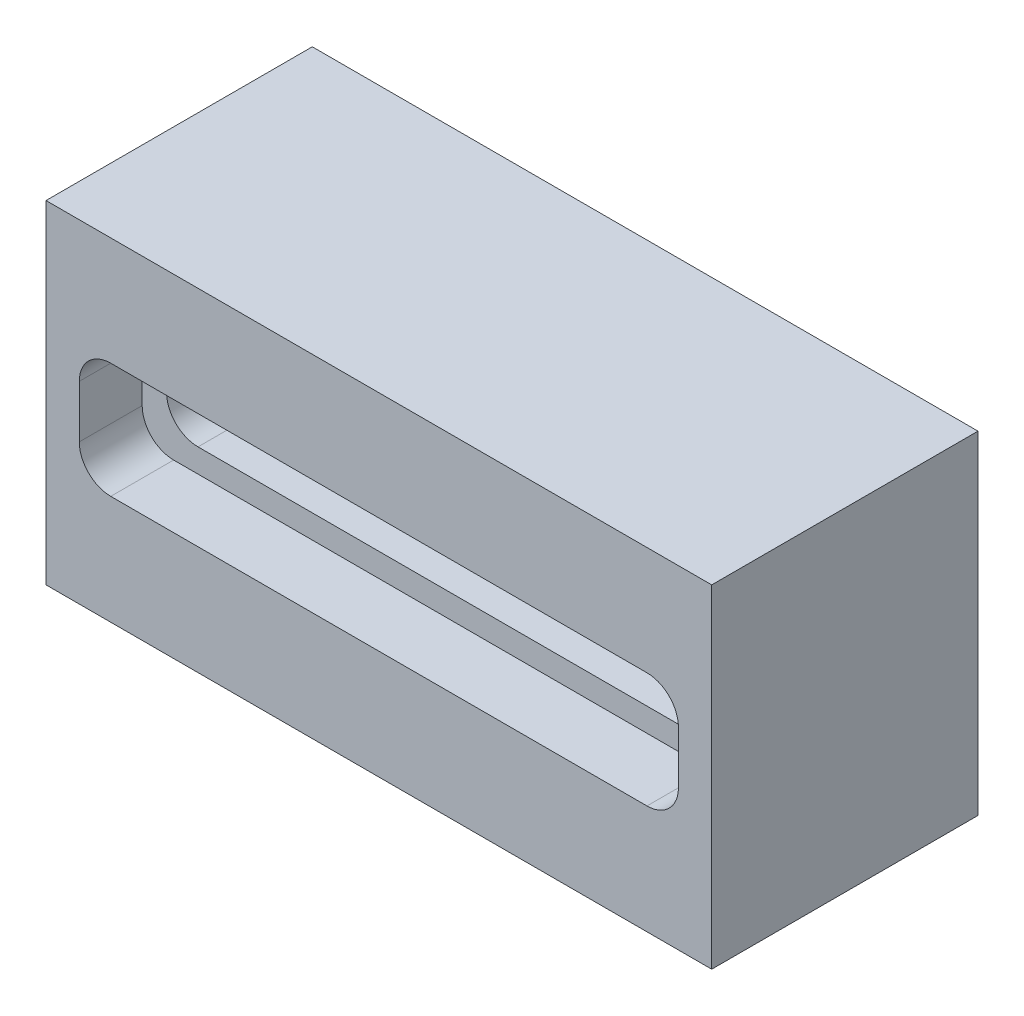
SolidWorks part; units mm, degrees
ref_plane "Front Plane" through (0, 0, 0) normal (0, 0, 1) x (1, 0, 0)
ref_plane "Top Plane" through (0, 0, 0) normal (0, 1, 0) x (1, 0, 0)
ref_plane "Right Plane" through (0, 0, 0) normal (1, 0, 0) x (0, 0, -1)
sketch "Sketch1" plane through (0, 0, 0) normal (0, 1, 0) x (1, 0, 0)
  line L1 (0, 0) -> (127, 0)
  line L2 (0, 0) -> (0, 50.8)
  line L3 (0, 50.8) -> (127, 50.8)
  line L4 (127, 0) -> (127, 50.8)
  dimension "D1" = 50.8
  dimension "D2" = 127
extrude "Boss-Extrude1" add sketch "Sketch1" along normal blind 63.5
sketch "Sketch2" plane through (0, 0, 0) normal (0, 0, 1) x (1, 0, 0)
  line L1 (0, 0) -> (63.5, 0)
  line L2 (0, 0) -> (0, 31.8)
  line L3 (0, 31.8) -> (63.5, 31.8)
  line L4 (63.5, 0) -> (63.5, 31.8)
  line L5 (17, 38.3) -> (110, 38.3)
  line L6 (11, 32.3) -> (11, 31.3)
  line L7 (17, 25.3) -> (110, 25.3)
  line L8 (116, 32.3) -> (116, 31.3)
  line L9 (11, 38.3) -> (116, 25.3) construction
  line L10 (11, 25.3) -> (116, 38.3) construction
  arc A0 (110, 38.3) -> (116, 32.3) centre (110, 32.3) cw
  arc A1 (110, 25.3) -> (116, 31.3) centre (110, 31.3) ccw
  arc A2 (11, 31.3) -> (17, 25.3) centre (17, 31.3) ccw
  arc A3 (17, 38.3) -> (11, 32.3) centre (17, 32.3) ccw
  dimension "D5" = 6
  dimension "D1" = 31.8
  dimension "D2" = 63.5
  dimension "D3" = 105
  dimension "D4" = 13
sketch "Sketch3" plane through (0, 0, 0) normal (0, 0, 1) x (1, 0, 0)
  line L1 (0, 0) -> (63.5, 0)
  line L2 (0, 0) -> (0, 31.8)
  line L3 (0, 31.8) -> (63.5, 31.8)
  line L4 (63.5, 0) -> (63.5, 31.8)
  line L5 (12.35, 42.8) -> (114.65, 42.8)
  line L6 (6.35, 36.8) -> (6.35, 26.8)
  line L7 (12.35, 20.8) -> (114.65, 20.8)
  line L8 (120.65, 36.8) -> (120.65, 26.8)
  line L9 (6.35, 42.8) -> (120.65, 20.8) construction
  line L10 (6.35, 20.8) -> (120.65, 42.8) construction
  arc A0 (12.35, 42.8) -> (6.35, 36.8) centre (12.35, 36.8) ccw
  arc A1 (6.35, 26.8) -> (12.35, 20.8) centre (12.35, 26.8) ccw
  arc A2 (114.65, 20.8) -> (120.65, 26.8) centre (114.65, 26.8) ccw
  arc A3 (114.65, 42.8) -> (120.65, 36.8) centre (114.65, 36.8) cw
  dimension "D4" = 6
  dimension "D1" = 63.5
  dimension "D2" = 31.8
  dimension "D3" = 114.3
  dimension "D5" = 10
extrude "Cut-Extrude2" cut sketch "Sketch3" against normal blind 12 contours L5 A3 L8 A2 L7 A1 L6 A0
extrude "Cut-Extrude3" cut sketch "Sketch2" against normal through all contours L5 A0 L8 A1 L7 A2 L6 A3
